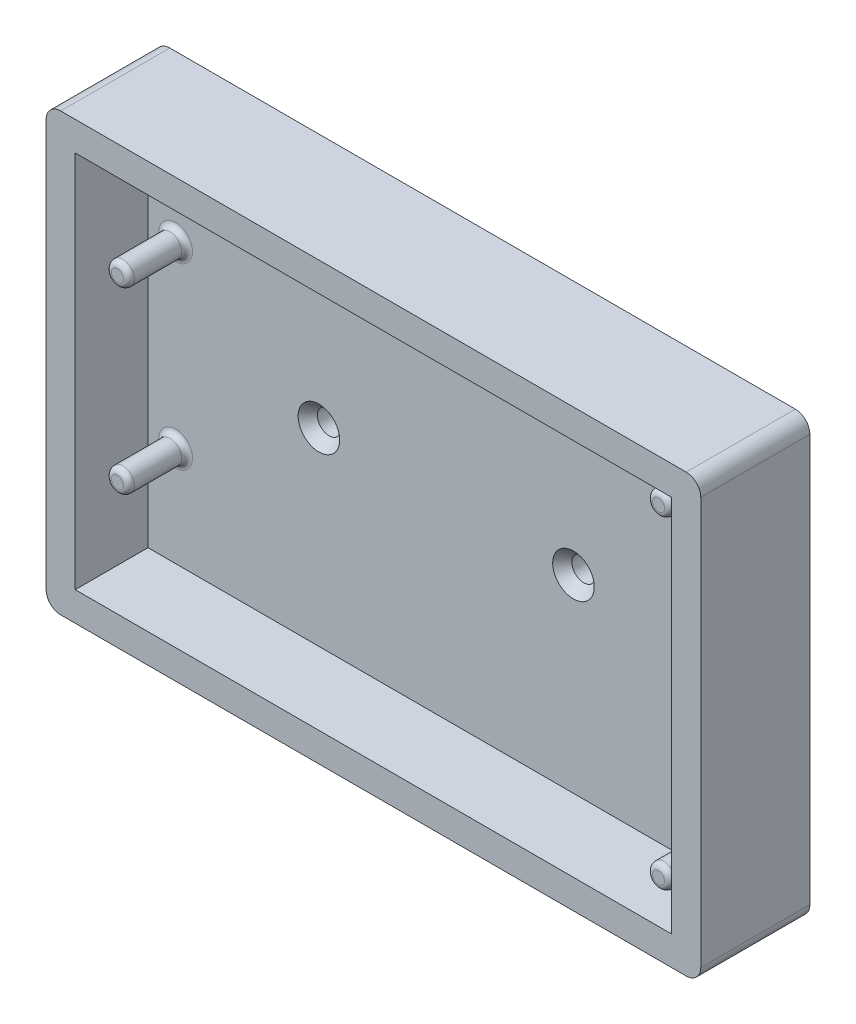
SolidWorks part; units mm, degrees
ref_plane "Plan de face" through (0, 0, 0) normal (0, 0, 1) x (1, 0, 0)
ref_plane "Plan de dessus" through (0, 0, 0) normal (0, 1, 0) x (1, 0, 0)
ref_plane "Plan de droite" through (0, 0, 0) normal (1, 0, 0) x (0, 0, -1)
sketch "Esquisse1" plane through (0, 0, 0) normal (0, 0, 1) x (1, 0, 0)
  line L1 (-45, 30) -> (45, 30)
  line L2 (-45, 30) -> (-45, -30)
  line L3 (-45, -30) -> (45, -30)
  line L4 (45, 30) -> (45, -30)
  line L5 (-45, 30) -> (45, -30) construction
  line L6 (-45, -30) -> (45, 30) construction
  point P0 (0, 0)
  dimension "D1" = 90
  dimension "D2" = 60
extrude "Boss.-Extru.1" add sketch "Esquisse1" along normal blind 5 contours L2 L3 L4 L1
sketch "Esquisse2" plane through (0, 0, 5) normal (0, 0, 1) x (1, 0, 0)
  line L0 (-45, 30) -> (45, 30) construction
  line L1 (-41, 26) -> (41, 26)
  line L2 (-41, 26) -> (-41, -26)
  line L3 (-41, -26) -> (41, -26)
  line L4 (41, 26) -> (41, -26)
  line L5 (-41, 26) -> (41, -26) construction
  line L6 (-41, -26) -> (41, 26) construction
  line L7 (-45, 30) -> (-45, -30) construction
  line L9 (-45, 30) -> (45, 30)
  line L10 (-45, 30) -> (-45, -30)
  line L11 (-45, -30) -> (45, -30)
  line L12 (45, 30) -> (45, -30)
  line L13 (-45, 30) -> (45, -30) construction
  line L14 (-45, -30) -> (45, 30) construction
  point P0 (0, 0)
  point P10 (0, 0)
  dimension "D1" = 4
  dimension "D2" = 4
extrude "Boss.-Extru.2" add sketch "Esquisse2" along normal blind 10
sketch "Esquisse3" plane through (0, 0, 5) normal (0, 0, 1) x (1, 0, 0)
  circle A0 centre (-37.2, 12.3) radius 1.575
  circle A1 centre (-37.2, -12.3) radius 1.575
  circle A2 centre (37.2, -22.2) radius 1.575
  circle A3 centre (37.2, 22.2) radius 1.575
  dimension "D1" = 3.15
extrude "Boss.-Extru.3" add sketch "Esquisse3" along normal blind 8
hole_wizard "Fraisage pour vis à tête fraisée bombée #41" positions "Esquisse5" profile "Esquisse7" countersink size "#4" standard "Ansi Inch" end condition through all
sketch "Esquisse5" plane through (0, 0, 5) normal (0, 0, 1) x (1, 0, 0)
  line L0 (-17.5, 0) -> (17.5, 0) construction
  point P0 (-17.5, 0)
  point P2 (17.5, 0)
  point P10 (0, 0)
  dimension "D1" = 35
sketch "Esquisse7" plane through (-17.5, 0, 5) normal (1, 0, 0) x (0, -1, 0)
  line L0 (0, 0) -> (0, 5)
  line L1 (0, 5) -> (1.6319, 5)
  line L2 (1.6319, 5) -> (1.6319, 1.4098)
  line L3 (1.6319, 1.4098) -> (2.8575, 0)
  line L5 (2.8575, 0) -> (0, 0)
  line L6 (-1.632, 1.4098) -> (-2.8575, 0) construction
  line L11 (0, -6.35) -> (0, 107.95) construction
  dimension "Diamètre du perçage jusqu'au prochain" = 3.2639
  dimension "Profondeur du perçage jusqu'au prochain" = 5
  dimension "Diamètre du fraisage entrant" = 5.715
  dimension "Angle du fraisage entrant" = 82
fillet "Congé1" radius 2 4 edges at (-45, -30, 7.5) (-45, 30, 7.5) (45, 30, 7.5) (45, -30, 7.5)
fillet "Congé2" radius 0.75 8 edges at (38.775, 22.2, 13) (-35.625, 12.3, 13) (35.625, 22.2, 5) (-38.775, 12.3, 5) (-38.775, -12.3, 5) (35.625, -22.2, 5) (-35.625, -12.3, 13) (38.775, -22.2, 13)
